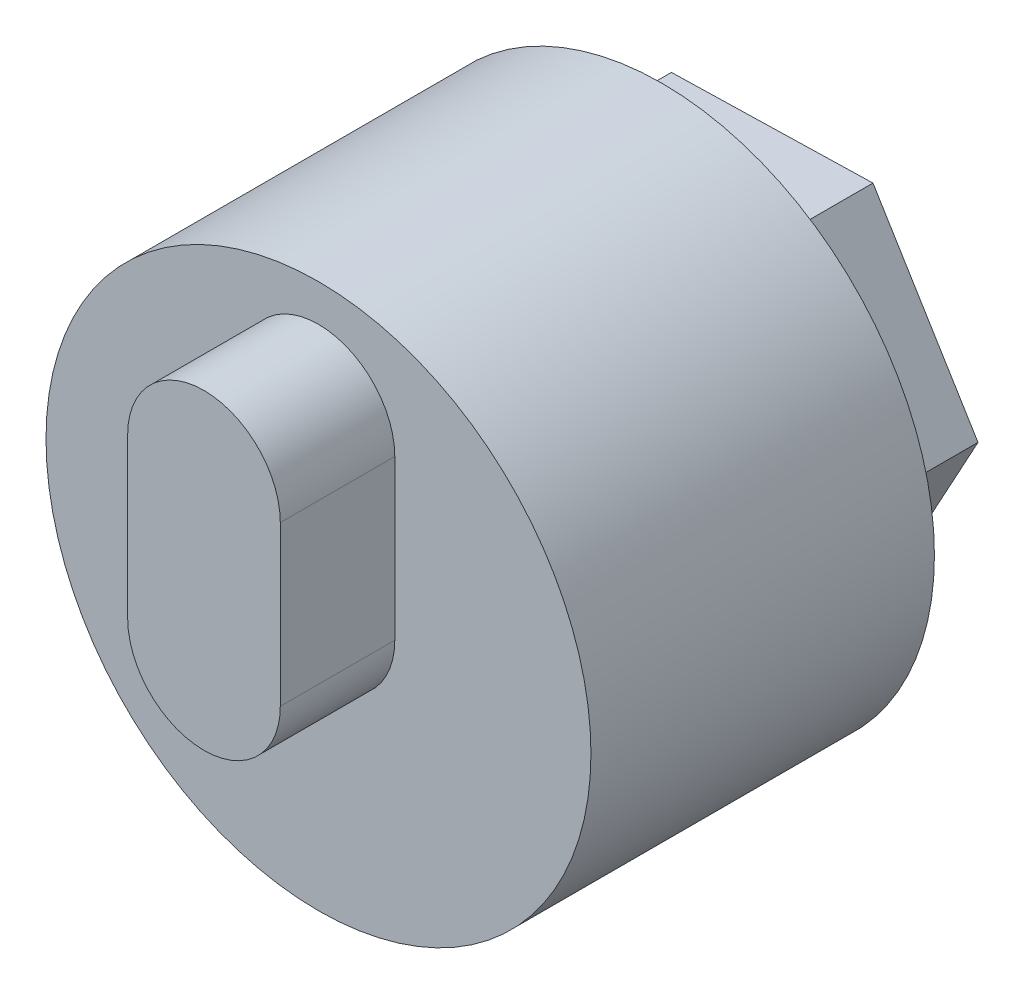
SolidWorks part; units mm, degrees
ref_plane "Спереди" through (0, 0, 0) normal (0, 0, 1) x (1, 0, 0)
ref_plane "Сверху" through (0, 0, 0) normal (0, 1, 0) x (1, 0, 0)
ref_plane "Справа" through (0, 0, 0) normal (1, 0, 0) x (0, 0, -1)
sketch "Эскиз1" plane through (0, 0, 0) normal (0, 0, 1) x (1, 0, 0)
  circle A0 centre (0, 0) radius 23.7976
extrude "Бобышка-Вытянуть1" add sketch "Эскиз1" along normal blind 30
sketch "Эскиз2" plane through (0, 0, 0) normal (0, 0, -1) x (-1, 0, 0)
  line L1 (8.4286, -15.4592) -> (17.6023, -0.4302)
  line L2 (17.6023, -0.4302) -> (9.1737, 15.029)
  line L3 (9.1737, 15.029) -> (-8.4286, 15.4592)
  line L4 (-8.4286, 15.4592) -> (-17.6023, 0.4302)
  line L5 (-17.6023, 0.4302) -> (-9.1737, -15.029)
  line L6 (-9.1737, -15.029) -> (8.4286, -15.4592)
  circle A0 centre (0, 0) radius 15.2486 construction
extrude "Бобышка-Вытянуть2" add sketch "Эскиз2" along normal blind 10
sketch "Эскиз3" plane through (0, 0, 30) normal (0, 0, 1) x (1, 0, 0)
  line L0 (0, 0) -> (0, 13.8979) construction
  line L1 (-6.6652, 0) -> (-6.6652, 13.8979)
  line L2 (6.6652, 0) -> (6.6652, 13.8979)
  arc A0 (-6.6652, 0) -> (6.6652, 0) centre (0, 0) ccw
  arc A1 (6.6652, 13.8979) -> (-6.6652, 13.8979) centre (0, 13.8979) ccw
  point P3 (0, 6.9489)
extrude "Бобышка-Вытянуть3" add sketch "Эскиз3" along normal blind 10
